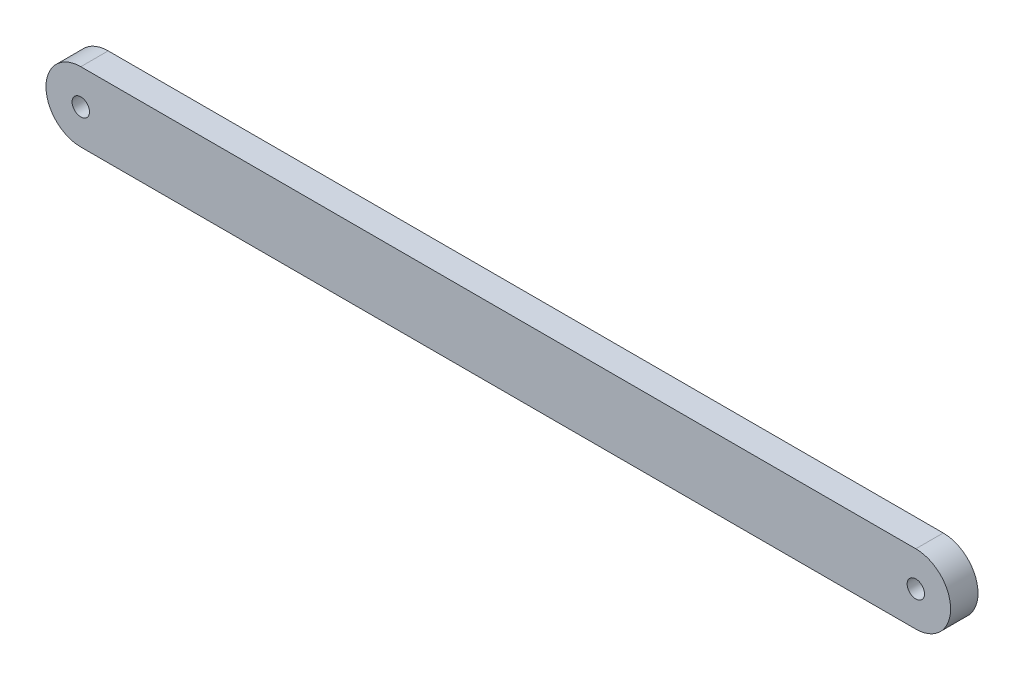
SolidWorks part; units mm, degrees
ref_plane "Front Plane" through (0, 0, 0) normal (0, 0, 1) x (1, 0, 0)
ref_plane "Top Plane" through (0, 0, 0) normal (0, 1, 0) x (1, 0, 0)
ref_plane "Right Plane" through (0, 0, 0) normal (1, 0, 0) x (0, 0, -1)
sketch "Sketch1" plane through (0, 0, 0) normal (0, 0, 1) x (1, 0, 0)
  line L0 (0, 12.7) -> (304.8, 12.7)
  line L1 (0, -12.7) -> (304.8, -12.7)
  arc A0 (0, 12.7) -> (0, -12.7) centre (0, 0) ccw
  arc A1 (304.8, -12.7) -> (304.8, 12.7) centre (304.8, 0) ccw
  circle A2 centre (0, 0) radius 3.175
  circle A3 centre (304.8, 0) radius 3.175
  dimension "D1" = 25.4
  dimension "D3" = 6.35
  dimension "D2" = 304.8
extrude "Boss-Extrude1" add sketch "Sketch1" along normal blind 10
